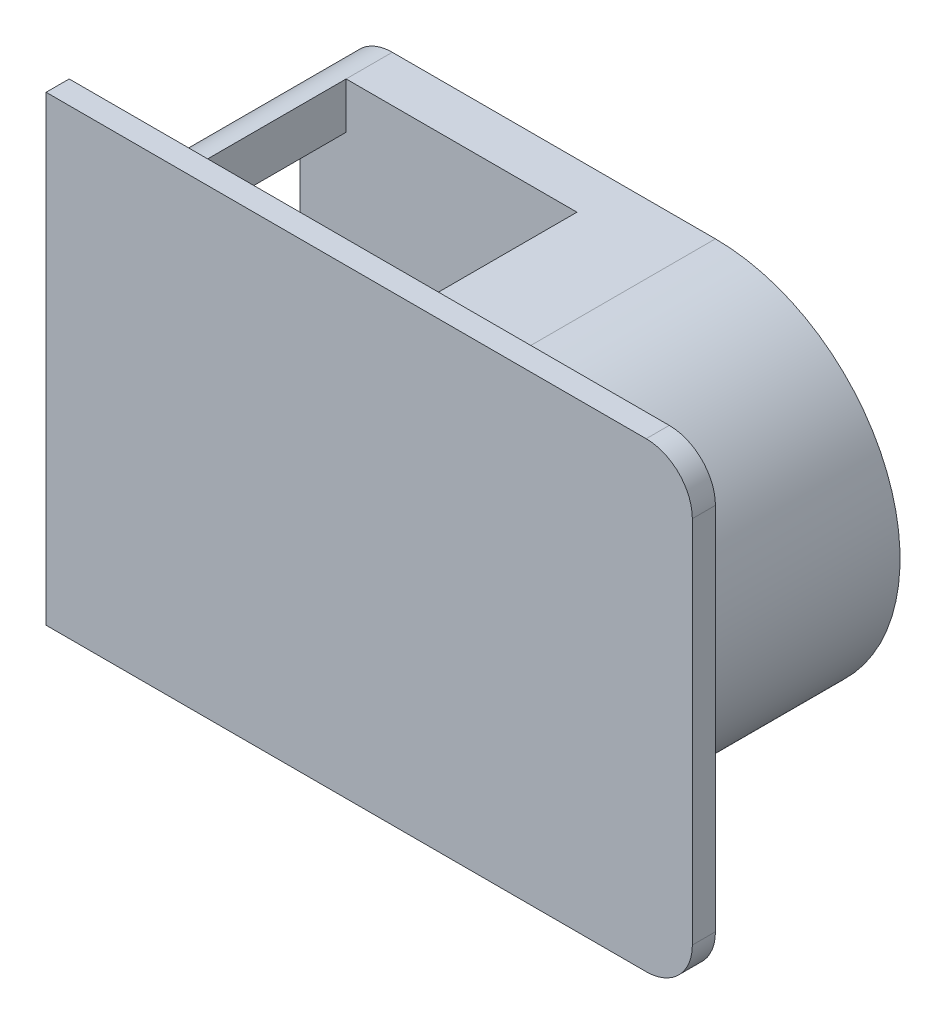
SolidWorks part; units mm, degrees
material "ABS"
ref_plane "Alzado" through (0, 0, 0) normal (0, 0, 1) x (1, 0, 0)
ref_plane "Planta" through (0, 0, 0) normal (0, 1, 0) x (1, 0, 0)
ref_plane "Vista lateral" through (0, 0, 0) normal (1, 0, 0) x (0, 0, -1)
sketch "Croquis1" plane through (0, 0, 0) normal (0, 0, 1) x (1, 0, 0)
  line L1 (-60, -40) -> (60, -40)
  line L2 (-60, -40) -> (-60, 40)
  line L3 (-60, 40) -> (60, 40)
  line L4 (60, -40) -> (60, 40)
  line L5 (-60, -40) -> (60, 40) construction
  line L6 (-60, 40) -> (60, -40) construction
  circle A0 centre (60, 0) radius 40
  circle A1 centre (20, 0) radius 40
  point P0 (0, 0)
  dimension "D1" = 120
  dimension "D2" = 80
extrude "Saliente-Extruir2" add sketch "Croquis1" along normal blind 50 contours A1 L3 L2 L1 | A0 A1 | A1 A0 region at (-34.8877, 0, 0) region at (7.1592, 0, 0) region at (40, 0, 0)
sketch "Croquis4" plane through (0, 0, 50) normal (0, 0, 1) x (1, 0, 0)
  line L1 (-70, -50) -> (70, -50)
  line L2 (-70, -50) -> (-70, 50)
  line L3 (-70, 50) -> (70, 50)
  line L4 (70, -50) -> (70, 50)
  line L5 (-70, -50) -> (70, 50) construction
  line L6 (-70, 50) -> (70, -50) construction
  point P0 (0, 0)
  dimension "D1" = 140
  dimension "D2" = 100
extrude "Saliente-Extruir3" add sketch "Croquis4" along normal blind 5
sketch "Croquis5" plane through (0, 0, 0) normal (0, 0, -1) x (-1, 0, 0)
  circle A0 centre (-20, 0) radius 30
  circle A1 centre (-20, 0) radius 5
extrude "Cortar-Extruir1" cut sketch "Croquis5" against normal blind 5 contours A1
sketch "Croquis6" plane through (0, 40, 0) normal (0, 1, 0) x (1, 0, 0)
  line L0 (-60, -50) -> (-60, 0) construction
  line L1 (-50, -50) -> (0, -50)
  line L2 (-50, -50) -> (-50, -10)
  line L3 (-50, -10) -> (0, -10)
  line L4 (0, -50) -> (0, -10)
  line L5 (-50, -50) -> (0, -10) construction
  line L6 (-50, -10) -> (0, -50) construction
  line L7 (-60, 0) -> (20, 0) construction
  line L9 (20, -50) -> (20, 0) construction
  line L10 (-60, -50) -> (20, -50) construction
  point P0 (-25, -30)
  dimension "D1" = 10
  dimension "D2" = 10
  dimension "D4" = 20
extrude "Cortar-Extruir2" cut sketch "Croquis6" against normal blind 80
sketch "Croquis7" plane through (-60, 0, 0) normal (-1, 0, 0) x (0, 0, 1)
  line L0 (0, -40) -> (0, 40) construction
  line L1 (10, -30) -> (50, -30)
  line L2 (10, -30) -> (10, 30)
  line L3 (10, 30) -> (50, 30)
  line L4 (50, -30) -> (50, 30)
  line L5 (10, -30) -> (50, 30) construction
  line L6 (10, 30) -> (50, -30) construction
  line L7 (50, 40) -> (0, 40) construction
  line L8 (50, -40) -> (0, -40) construction
  line L10 (50, 50) -> (50, -50) construction
  point P0 (30, 0)
  dimension "D1" = 10
  dimension "D2" = 10
  dimension "D3" = 10
  dimension "D4" = 0
extrude "Cortar-Extruir3" cut sketch "Croquis7" against normal blind 50
sketch "Croquis8" plane through (0, 0, 0) normal (0, 0, -1) x (-1, 0, 0)
  line L0 (60, -40) -> (60, 40) construction
  circle A0 centre (30, 0) radius 2.5
  circle A1 centre (-20, 0) radius 30
  circle A2 centre (30, 0) radius 10
  dimension "D1" = 30
  dimension "D2" = 5
extrude "Cortar-Extruir5" cut sketch "Croquis8" against normal blind 20 contours A0
fillet "Redondeo1" radius 10 1 edges at (70, -50, 52.5)
fillet "Redondeo2" radius 10 1 edges at (70, 50, 52.5)
fillet "Redondeo3" radius 10 1 edges at (-60, -40, 25)
fillet "Redondeo4" radius 10 1 edges at (-60, 40, 25)
